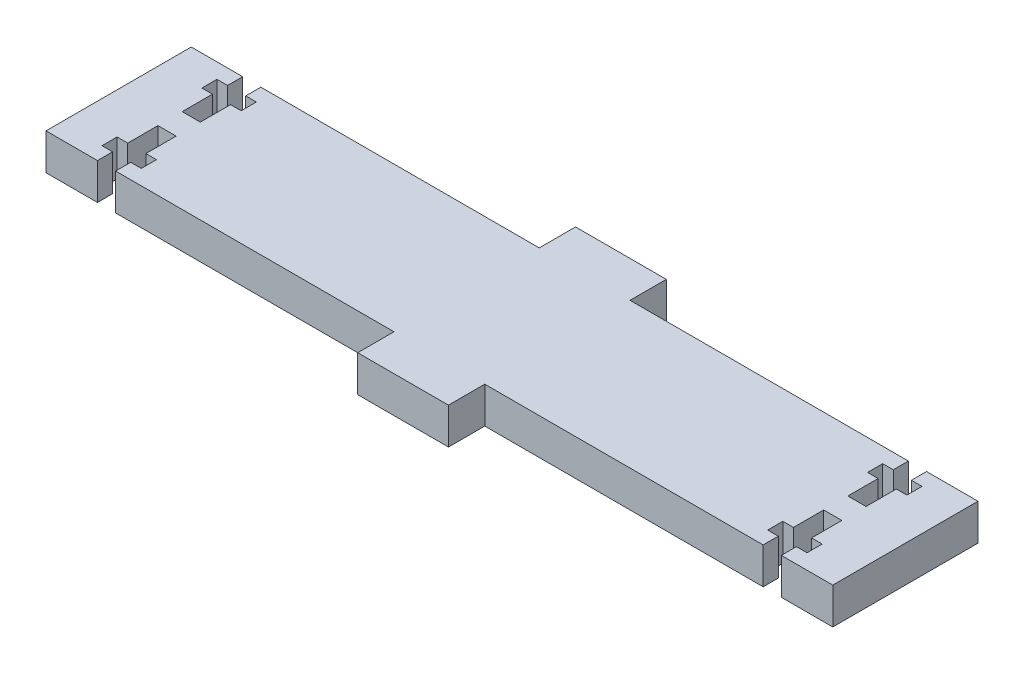
SolidWorks part; units mm, degrees
ref_plane "Front Plane" through (0, 0, 0) normal (0, 0, 1) x (1, 0, 0)
ref_plane "Top Plane" through (0, 0, 0) normal (0, 1, 0) x (1, 0, 0)
ref_plane "Right Plane" through (0, 0, 0) normal (1, 0, 0) x (0, 0, -1)
sketch "Sketch1" plane through (0, 0, 0) normal (0, 1, 0) x (1, 0, 0)
  line L0 (-1342.2955, 0) -> (65772.4784, 0) construction
  line L1 (0, -1342.2955) -> (0, 65772.4784) construction
  line L2 (-55, 12) -> (-55, -12) construction
  line L3 (-65, 12) -> (65, 12)
  line L4 (-65, 12) -> (-65, -12)
  line L5 (-65, -12) -> (65, -12)
  line L6 (65, 12) -> (65, -12)
  line L7 (-65, 12) -> (65, -12) construction
  line L8 (-65, -12) -> (65, 12) construction
  line L9 (-56.5, 12) -> (-53.5, 12)
  line L10 (-56.5, 12) -> (-56.5, 2)
  line L11 (-56.5, 2) -> (-53.5, 2)
  line L12 (-53.5, 12) -> (-53.5, 2)
  line L13 (-58.25, 9.5) -> (-51.75, 9.5)
  line L14 (-58.25, 9.5) -> (-58.25, 7)
  line L15 (-58.25, 7) -> (-51.75, 7)
  line L16 (-51.75, 9.5) -> (-51.75, 7)
  line L17 (55, 12) -> (55, -12) construction
  line L18 (51.75, 9.5) -> (51.75, 7)
  line L19 (58.25, 7) -> (51.75, 7)
  line L20 (58.25, 9.5) -> (58.25, 7)
  line L21 (58.25, 9.5) -> (51.75, 9.5)
  line L22 (53.5, 12) -> (53.5, 2)
  line L23 (56.5, 2) -> (53.5, 2)
  line L24 (56.5, 12) -> (56.5, 2)
  line L25 (56.5, 12) -> (53.5, 12)
  line L26 (56.5, -12) -> (53.5, -12)
  line L27 (56.5, -12) -> (56.5, -2)
  line L28 (56.5, -2) -> (53.5, -2)
  line L29 (53.5, -12) -> (53.5, -2)
  line L30 (58.25, -9.5) -> (51.75, -9.5)
  line L31 (58.25, -9.5) -> (58.25, -7)
  line L32 (58.25, -7) -> (51.75, -7)
  line L33 (51.75, -9.5) -> (51.75, -7)
  line L34 (-51.75, -9.5) -> (-51.75, -7)
  line L35 (-58.25, -7) -> (-51.75, -7)
  line L36 (-58.25, -9.5) -> (-58.25, -7)
  line L37 (-58.25, -9.5) -> (-51.75, -9.5)
  line L38 (-53.5, -12) -> (-53.5, -2)
  line L39 (-56.5, -2) -> (-53.5, -2)
  line L40 (-56.5, -12) -> (-56.5, -2)
  line L41 (-56.5, -12) -> (-53.5, -12)
  line L42 (-7.5, -12) -> (7.5, -18) construction
  line L43 (-7.5, 18) -> (7.5, 18)
  line L44 (-7.5, 18) -> (-7.5, 12)
  line L45 (-7.5, 12) -> (7.5, 12)
  line L46 (7.5, 18) -> (7.5, 12)
  line L47 (-7.5, 18) -> (7.5, 12) construction
  line L48 (-7.5, 12) -> (7.5, 18) construction
  line L49 (-7.5, -18) -> (7.5, -12) construction
  line L50 (7.5, -18) -> (7.5, -12)
  line L51 (-7.5, -12) -> (7.5, -12)
  line L52 (-7.5, -18) -> (-7.5, -12)
  line L53 (-7.5, -18) -> (7.5, -18)
  point P4 (0, 0)
  point P46 (0, 15)
  point P51 (0, 0)
  point P56 (0, -15)
  dimension "D1" = 130
  dimension "D2" = 24
  dimension "D3" = 10
  dimension "D4" = 3
  dimension "D5" = 6.5
  dimension "D6" = 2.5
  dimension "D7" = 5
  dimension "D9" = 55
  dimension "D8" = 55
  dimension "D10" = 15
  dimension "D11" = 6
extrude "Boss-Extrude1" add sketch "Sketch1" along normal blind 6 contours L5 L40 L37 L36 L35 L39 L38 L34 L29 L30 L33 L32 L28 L27 L31 L6 L3 L24 L21 L20 L19 L23 L22 L18 L12 L13 L16 L15 L11 L10 L14 | L46 L43 L44 L3 | L52 L53 L50 L5 region at (0, 0, 0) region at (0, 0, -15) region at (0, 0, 15)
equation "\"Frame_Size\" = 220"
equation "\"Frame_Thickness\" = 6"
equation "\"Arm_Width\" = 30"
equation "\"Motor_Mount_Hole_Diameter\" = 8"
equation "\"Motor_Shaft_Diameter\" = 3"
equation "\"Screw_Nut_Diameter\" = 6.5"
equation "\"Screw_Diameter\" = 3"
equation "\"Screw_Shaft_Length\" = 10"
equation "\"Screw_Hole_Separation_C2C\" = 20"
equation "\"Solder_Board_Small_Screw_Hole_Separation\" = 37"
equation "\"Solder_Board_Small_Screw_Hole_Diameter\" = 3.3"
equation "\"Solder_Board_Small_Length\" = 45.72"
equation "\"Solder_Board_Small_Width\" = 33.02"
equation "\"Solder_Board_Small_Thickness\" = 1.6"
equation "\"ESC_Length\" = 35"
equation "\"ESC_Width\" = 17"
equation "\"ESC_Thickness\" = 5"
equation "\"Battery_Length\" = 105"
equation "\"Battery_Width\" = 33"
equation "\"Battery_Thickness\" = 24"
equation "\"Battery_Holder_Screw_Hole_Distance_Long\" = 110"
equation "\"Battery_Holder_Screw_Hole_Distance_Short\" = 40"
equation "\"D1@Sketch1\"=\"Battery_Holder_Screw_Hole_Distance_Long\"+ 20"
equation "\"D2@Sketch1\"=\"Battery_Thickness\""
equation "\"D3@Sketch1\"=\"Screw_Shaft_Length\""
equation "\"D4@Sketch1\"=\"Screw_Diameter\""
equation "\"D5@Sketch1\"=\"Screw_Nut_Diameter\""
equation "\"Screw_Nut_Thickness\" = 2.5"
equation "\"D6@Sketch1\"=\"Screw_Nut_Thickness\""
equation "\"D7@Sketch1\"=\"Screw_Shaft_Length\"/2"
equation "\"D9@Sketch1\"=\"Battery_Holder_Screw_Hole_Distance_Long\"/2"
equation "\"D8@Sketch1\"=\"Battery_Holder_Screw_Hole_Distance_Long\"/2"
equation "\"D1@Boss-Extrude1\"=\"Frame_Thickness\""
equation "\"Tooth_Width\" = 15"
equation "\"D10@Sketch1\"=\"Tooth_Width\""
equation "\"D11@Sketch1\"=\"Frame_Thickness\""
